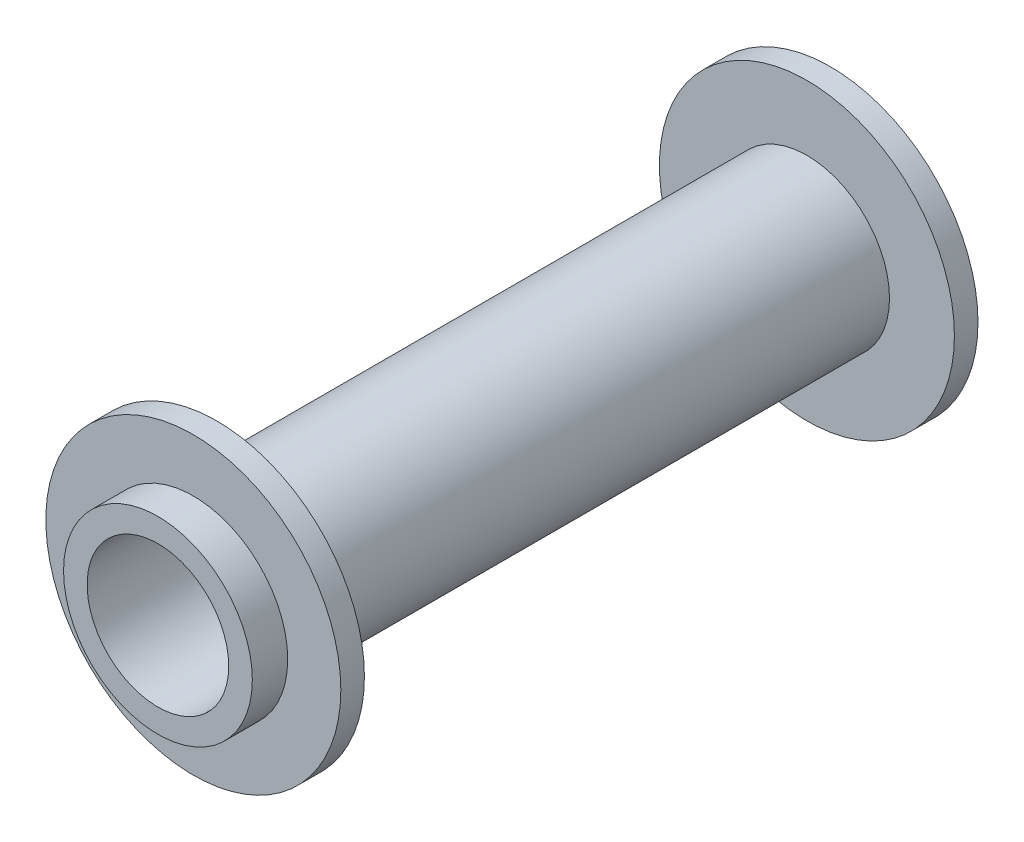
SolidWorks part; units mm, degrees
material "POM Acetal Copolymer"
ref_plane "Front Plane" through (0, 0, 0) normal (0, 0, 1) x (1, 0, 0)
ref_plane "Top Plane" through (0, 0, 0) normal (0, 1, 0) x (1, 0, 0)
ref_plane "Right Plane" through (0, 0, 0) normal (1, 0, 0) x (0, 0, -1)
sketch "Sketch1" plane through (0, 0, 0) normal (1, 0, 0) x (0, 0, -1)
  line L0 (0, 6) -> (60, 6)
  line L1 (60, 6) -> (60, 8)
  line L2 (60, 8) -> (57, 8)
  line L3 (57, 8) -> (57, 12.5)
  line L4 (57, 12.5) -> (55, 12.5)
  line L5 (55, 12.5) -> (55, 7)
  line L6 (55, 7) -> (5, 7)
  line L7 (5, 7) -> (5, 12.5)
  line L8 (5, 12.5) -> (3, 12.5)
  line L9 (3, 12.5) -> (3, 8)
  line L10 (3, 8) -> (0, 8)
  line L11 (0, 8) -> (0, 6)
  line L12 (0, 0) -> (60, 0) construction
  dimension "D1" = 60
  dimension "D2" = 8
  dimension "D3" = 12.5
  dimension "D4" = 6
  dimension "D5" = 1
  dimension "D6" = 3
  dimension "D7" = 2
revolve "Revolve1" add sketch "Sketch1" angle 360 about L12
